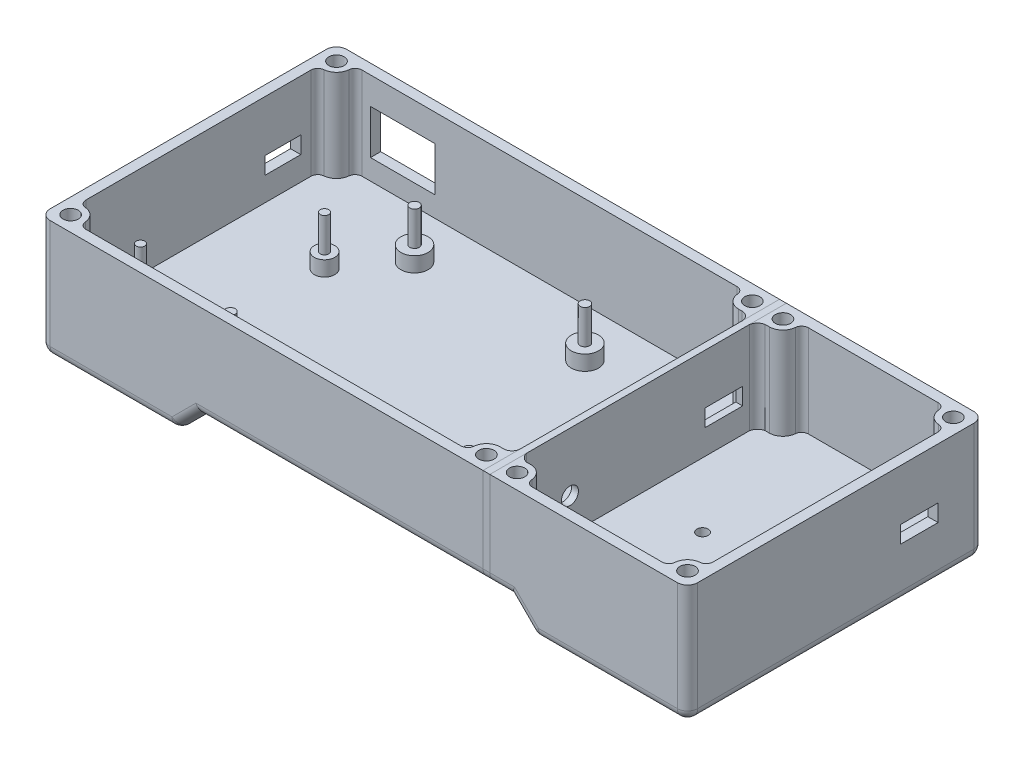
SolidWorks part; units mm, degrees
ref_plane "Front Plane" through (0, 0, 0) normal (0, 0, 1) x (1, 0, 0)
ref_plane "Top Plane" through (0, 0, 0) normal (0, 1, 0) x (1, 0, 0)
ref_plane "Right Plane" through (0, 0, 0) normal (1, 0, 0) x (0, 0, -1)
sketch "Sketch1" plane through (0, 0, 0) normal (0, 1, 0) x (1, 0, 0)
  line L0 (39, 43.5) -> (39, -43.5)
  line L1 (-89, -43.5) -> (89, -43.5)
  line L2 (-89, -43.5) -> (-89, 43.5)
  line L3 (-89, 43.5) -> (89, 43.5)
  line L4 (89, -43.5) -> (89, 43.5)
  line L5 (-89, -43.5) -> (89, 43.5) construction
  line L6 (-89, 43.5) -> (89, -43.5) construction
  line L7 (41, 43.5) -> (41, -43.5)
  point P0 (0, 0)
  dimension "D1" = 178
  dimension "D2" = 87
  dimension "D3" = 128
  dimension "D4" = 48
extrude "Boss-Extrude1" add sketch "Sketch1" along normal mid plane 35 contours L3 L2 L1 L0 region at (-25, 0, 0)
extrude "Boss-Extrude3" add sketch "Sketch1<4>" along normal mid plane 35 separate body contours L3 L7 L1 L4 region at (65, 0, 0)
sketch "Sketch1<4>" plane through (0, 0, 0) normal (0, 1, 0) x (1, 0, 0) same geometry as "Sketch1"
extrude "Boss-Extrude4" add sketch "Sketch1<5>" along normal mid plane 35 separate body contours L7 L3 L0 L1 region at (40, 0, 0)
sketch "Sketch1<5>" plane through (0, 0, 0) normal (0, 1, 0) x (1, 0, 0) same geometry as "Sketch1"
sketch "Sketch2" plane through (0, 17.5, 0) normal (0, 1, 0) x (1, 0, 0)
  line L0 (-89, -43.5) -> (-89, 43.5) construction
  line L1 (-89, 43.5) -> (39, 43.5) construction
  line L2 (-89, -43.5) -> (39, -43.5) construction
  line L3 (39, 43.5) -> (39, -43.5) construction
  point P0 (-84.5, 39)
  point P1 (35.5, -39)
  point P2 (-84.5, -39)
  point P3 (35.5, 39)
  dimension "D1" = 4.5
  dimension "D2" = 4.5
  dimension "D3" = 4.5
  dimension "D4" = 3.5
sketch "Sketch5" plane through (0, 17.5, 0) normal (0, 1, 0) x (1, 0, 0)
  line L0 (41, 43.5) -> (41, -43.5) construction
  line L1 (89, -43.5) -> (89, 43.5) construction
  line L2 (41, -43.5) -> (89, -43.5) construction
  line L3 (41, 43.5) -> (89, 43.5) construction
  point P0 (44.5, 39)
  point P1 (84.5, 39)
  point P2 (44.5, -39)
  point P3 (84.5, -39)
  dimension "D2" = 4.5
  dimension "D3" = 4.5
  dimension "D1" = 3.5
  dimension "D4" = 4.5
sketch "Sketch8" plane through (0, 17.5, 0) normal (0, 1, 0) x (1, 0, 0)
  line L0 (89, -43.5) -> (89, 43.5) construction
  line L1 (48.2081, -40.5) -> (80.7919, -40.5)
  line L2 (41, -32.6771) -> (41, 32.6771)
  line L3 (48.2081, 40.5) -> (80.7919, 40.5)
  line L4 (86, -35.2919) -> (86, 35.2919)
  line L5 (43.9355, -35.0001) -> (83.1881, 35.2213) construction
  line L6 (43.9355, 35.0001) -> (83.1881, -35.2213) construction
  line L7 (41, -43.5) -> (89, -43.5) construction
  line L8 (41, 43.5) -> (41, -43.5) construction
  line L10 (43.2532, 35.0001) -> (44.5308, 35.0001)
  line L11 (-93.9988, 0) -> (111.049, 0) construction
  line L12 (43.2532, -35.0001) -> (44.5308, -35.0001)
  arc A0 (80.7919, 40.5) -> (86, 35.2919) centre (84.5, 39) ccw
  arc A1 (48.2081, 40.5) -> (44.5308, 35.0001) centre (44.5, 39) cw
  arc A2 (43.2532, 35.0001) -> (41, 32.6771) centre (43.8563, 32.1609) ccw
  arc A3 (80.7919, -40.5) -> (86, -35.2919) centre (84.5, -39) cw
  arc A4 (43.2532, -35.0001) -> (41, -32.6771) centre (43.8563, -32.1609) cw
  arc A5 (48.2081, -40.5) -> (44.5308, -35.0001) centre (44.5, -39) ccw
  point P0 (63.5, 0)
  dimension "D7" = 4
  dimension "D2" = 3
  dimension "D3" = 3
  dimension "D4" = 0
extrude "Cut-Extrude1" cut sketch "Sketch8" against normal offset from surface (27 mm away) 8 up to face at (65, -17.5, 0)
fillet "Fillet1" radius 2 6 edges at (48.2081, 4, 40.5) (80.7919, 4, 40.5) (86, 4, 35.2919) (80.7919, 4, -40.5) (86, 4, -35.2919) (48.2081, 4, -40.5)
sketch "Sketch10" plane through (0, 17.5, 0) normal (0, 1, 0) x (1, 0, 0)
  line L0 (-89, 43.5) -> (39, 43.5) construction
  line L1 (-80.7919, -40.5) -> (31.7919, -40.5)
  line L2 (-86, -35.2919) -> (-86, 35.2919)
  line L3 (-80.7919, 40.5) -> (31.7919, 40.5)
  line L4 (39, -32.5) -> (39, 32.5)
  line L5 (-80.9229, -37.21) -> (32.5375, 36.3123) construction
  line L6 (-80.9229, 37.21) -> (32.5375, -36.3123) construction
  line L7 (-89, -43.5) -> (-89, 43.5) construction
  line L8 (39, 43.5) -> (39, -43.5) construction
  line L10 (35.5, 35) -> (36.5, 35)
  line L11 (-113.4699, 0) -> (103.1317, 0) construction
  line L12 (35.5, -35) -> (36.5, -35)
  arc A0 (-80.7919, 40.5) -> (-86, 35.2919) centre (-84.5, 39) cw
  arc A1 (31.7919, 40.5) -> (35.5, 35) centre (35.5, 39) ccw
  arc A2 (36.5, 35) -> (39, 32.5) centre (36.5, 32.5) cw
  arc A3 (31.7919, -40.5) -> (35.5, -35) centre (35.5, -39) cw
  arc A4 (36.5, -35) -> (39, -32.5) centre (36.5, -32.5) ccw
  arc A5 (-80.7919, -40.5) -> (-86, -35.2919) centre (-84.5, -39) ccw
  point P0 (-23.5, 0)
  dimension "D5" = 2.5
  dimension "D2" = 3
  dimension "D3" = 3
  dimension "D4" = 0
extrude "Cut-Extrude2" cut sketch "Sketch10" against normal offset from surface (27 mm away) 8 up to face at (-25, -17.5, 0)
fillet "Fillet2" radius 2 6 edges at (31.7919, 4, 40.5) (-80.7919, 4, 40.5) (-86, 4, 35.2919) (-80.7919, 4, -40.5) (-86, 4, -35.2919) (31.7919, 4, -40.5)
sketch "Sketch11" plane through (0, -9.5, 0) normal (0, 1, 0) x (1, 0, 0)
  line L0 (-78.5209, -40.5) -> (29.5209, -40.5) construction
  line L2 (-86, -33.0209) -> (-86, 33.0209) construction
  line L4 (-86, 33.0209) -> (-86, -33.0209) construction
  circle A0 centre (-51.05, 26.45) radius 4
  circle A1 centre (-1.05, 26.45) radius 4
  circle A2 centre (-51.05, -27.55) radius 4
  circle A3 centre (18.95, -27.55) radius 3.5
  circle A4 centre (-62.5, 11.5) radius 3
  circle A5 centre (-79.5, -23.5) radius 3
  point P22 (-79.5, -23.5)
  dimension "D3" = 8
  dimension "D4" = 7
  dimension "D8" = 8
  dimension "D9" = 8
  dimension "D14" = 6
  dimension "D2" = 54
  dimension "D10" = 6
  dimension "D6" = 35
  dimension "D1" = 12.95
  dimension "D5" = 34.95
  dimension "D7" = 17
  dimension "D12" = 6.5
  dimension "D13" = 17
  dimension "D15" = 70
  dimension "D16" = 50
extrude "Boss-Extrude5" add sketch "Sketch11" along normal blind 4.4
ref_plane "Plane1" through (0, -5.1, 0) normal (0, 1, 0) x (1, 0, 0)
sketch "Sketch12" plane through (0, -5.1, 0) normal (0, 1, 0) x (1, 0, 0)
  circle A0 centre (-51.05, 26.45) radius 1.4
  circle A1 centre (-51.05, 26.45) radius 4 construction
  circle A2 centre (-1.05, 26.45) radius 1.4
  circle A3 centre (18.95, -27.55) radius 1.4
  circle A4 centre (-51.05, -27.55) radius 1.4
  circle A5 centre (-62.5, 11.5) radius 1.25
  circle A7 centre (-1.05, 26.45) radius 4 construction
  circle A8 centre (18.95, -27.55) radius 3.5 construction
  circle A9 centre (-51.05, -27.55) radius 4 construction
  circle A10 centre (-62.5, 11.5) radius 3 construction
  circle A11 centre (-79.5, -23.5) radius 1.25
  dimension "D8" = 2.5
  dimension "D9" = 2.8
  dimension "D10" = 2.8
  dimension "D11" = 2.8
  dimension "D12" = 2.8
  dimension "D6" = 2.5
  dimension "D1" = 0
  dimension "D2" = 0
  dimension "D3" = 0
  dimension "D4" = 0
  dimension "D5" = 0
sketch "Sketch17" plane through (41, 0, 0) normal (1, 0, 0) x (0, 0, -1)
  line L0 (0, 23.5982) -> (0, -22.9808) construction
  line L1 (32.6771, -9.5) -> (32.6771, 17.5) construction
  line L2 (19.6771, -2.1913) -> (30.6771, -2.1913)
  line L3 (19.6771, -2.1913) -> (19.6771, 2.8087)
  line L4 (19.6771, 2.8087) -> (30.6771, 2.8087)
  line L5 (30.6771, -2.1913) -> (30.6771, 2.8087)
  line L6 (19.6771, -2.1913) -> (30.6771, 2.8087) construction
  line L7 (19.6771, 2.8087) -> (30.6771, -2.1913) construction
  circle A0 centre (-20, 0.3087) radius 2.5
  dimension "D1" = 5
  dimension "D3" = 20
  dimension "D2" = 2
  dimension "D4" = 11
  dimension "D5" = 5
extrude "Cut-Extrude4" cut sketch "Sketch17" against normal blind 10
sketch "Sketch21" plane through (-86, 0, 0) normal (1, 0, 0) x (0, 0, -1)
  line L2 (19.5209, -2.5) -> (30.0209, -2.5)
  line L3 (19.5209, -2.5) -> (19.5209, 2.5)
  line L4 (19.5209, 2.5) -> (30.0209, 2.5)
  line L5 (30.0209, -2.5) -> (30.0209, 2.5)
  line L6 (19.5209, -2.5) -> (30.0209, 2.5) construction
  line L7 (19.5209, 2.5) -> (30.0209, -2.5) construction
  dimension "D3" = 10.5
  dimension "D4" = 5
sketch "Sketch24" plane through (0, 0, -40.5) normal (0, 0, 1) x (1, 0, 0)
  line L0 (-78.5209, 17.5) -> (-78.5209, -9.5) construction
  line L1 (-78.0209, -3.5) -> (-59.0209, -3.5)
  line L2 (-78.0209, -3.5) -> (-78.0209, 9.5)
  line L3 (-78.0209, 9.5) -> (-59.0209, 9.5)
  line L4 (-59.0209, -3.5) -> (-59.0209, 9.5)
  line L5 (-78.0209, -3.5) -> (-59.0209, 9.5) construction
  line L6 (-78.0209, 9.5) -> (-59.0209, -3.5) construction
  line L7 (-78.5209, -9.5) -> (29.5209, -9.5) construction
  point P0 (-68.5209, 3)
  dimension "D1" = 13
  dimension "D2" = 19
  dimension "D3" = 0.5
  dimension "D4" = 6
sketch "Sketch25" plane through (0, 17.5, 0) normal (0, 1, 0) x (1, 0, 0)
  circle A0 centre (44.5, 39) radius 2.25
  circle A1 centre (84.5, 39) radius 2.25
  circle A2 centre (84.5, -39) radius 2.25
  circle A3 centre (44.5, -39) radius 2.25
  dimension "D1" = 4.5
  dimension "D2" = 4.5
  dimension "D3" = 4.5
  dimension "D4" = 4.5
extrude "Cut-Extrude8" cut sketch "Sketch25" against normal blind 12
sketch "Sketch26" plane through (0, 17.5, 0) normal (0, 1, 0) x (1, 0, 0)
  circle A0 centre (35.5, -39) radius 2.25
  circle A1 centre (-84.5, -39) radius 2.25
  circle A2 centre (-84.5, 39) radius 2.25
  circle A3 centre (35.5, 39) radius 2.25
  dimension "D1" = 4.5
  dimension "D2" = 4.5
  dimension "D3" = 4.5
  dimension "D4" = 4.5
extrude "Boss-Extrude6" add sketch "Sketch12" along normal blind 10
extrude "Cut-Extrude11" cut sketch "Sketch21" against normal through all
extrude "Cut-Extrude12" cut sketch "Sketch26" against normal blind 12
ref_plane "Plane3" through (-75, 0, 0) normal (-1, 0, 0) x (0, 0, 1)
split "Split2" trim tools "Plane3" bodies to split 130 resulting bodies 131 132
move or copy body "Body-Move/Copy3" bodies to move or copy 131 copy no translate (-2, 0, 0)
sketch "Sketch29" plane through (-77, 0, 0) normal (1, 0, 0) x (0, 0, -1)
  line L8 (43.5, -17.5) -> (43.5, 17.5)
  line L9 (43.5, 17.5) -> (40.5, 17.5)
  line L10 (40.5, 17.5) -> (40.5, -9.5)
  line L11 (40.5, -9.5) -> (-40.5, -9.5)
  line L12 (-40.5, -9.5) -> (-40.5, 17.5)
  line L13 (-40.5, 17.5) -> (-43.5, 17.5)
  line L14 (-43.5, 17.5) -> (-43.5, -17.5)
  line L15 (-43.5, -17.5) -> (43.5, -17.5)
  line L16 (43.5, -17.5) -> (43.5, 17.5)
  line L17 (43.5, 17.5) -> (40.5, 17.5)
  line L18 (40.5, 17.5) -> (40.5, -9.5)
  line L19 (40.5, -9.5) -> (-40.5, -9.5)
  line L20 (-40.5, -9.5) -> (-40.5, 17.5)
  line L21 (-40.5, 17.5) -> (-43.5, 17.5)
  line L22 (-43.5, 17.5) -> (-43.5, -17.5)
  line L23 (-43.5, -17.5) -> (43.5, -17.5)
  dimension "D1" = 0
extrude "Boss-Extrude8" add sketch "Sketch29" along normal blind 2
extrude "Cut-Extrude13" cut sketch "Sketch24" against normal through all
ref_plane "Plane4" through (65, 0, 0) normal (1, 0, 0) x (0, 0, -1)
split "Split3" trim tools "Plane4" bodies to split 118 resulting bodies 136 137
move or copy body "Body-Move/Copy5" bodies to move or copy 136 copy no translate (10, 0, 0)
sketch "Sketch31" plane through (65, 0, 0) normal (1, 0, 0) x (0, 0, -1)
  line L8 (43.5, 17.5) -> (40.5, 17.5)
  line L9 (40.5, 17.5) -> (40.5, -9.5)
  line L10 (40.5, -9.5) -> (-40.5, -9.5)
  line L11 (-40.5, -9.5) -> (-40.5, 17.5)
  line L12 (-40.5, 17.5) -> (-43.5, 17.5)
  line L13 (-43.5, 17.5) -> (-43.5, -17.5)
  line L14 (-43.5, -17.5) -> (43.5, -17.5)
  line L15 (43.5, -17.5) -> (43.5, 17.5)
  line L16 (43.5, 17.5) -> (40.5, 17.5)
  line L17 (40.5, 17.5) -> (40.5, -9.5)
  line L18 (40.5, -9.5) -> (-40.5, -9.5)
  line L19 (-40.5, -9.5) -> (-40.5, 17.5)
  line L20 (-40.5, 17.5) -> (-43.5, 17.5)
  line L21 (-43.5, 17.5) -> (-43.5, -17.5)
  line L22 (-43.5, -17.5) -> (43.5, -17.5)
  line L23 (43.5, -17.5) -> (43.5, 17.5)
  dimension "D1" = 0
extrude "Boss-Extrude9" add sketch "Sketch31" along normal blind 13
sketch "Sketch32" plane through (0, 0, -43.5) normal (0, 0, -1) x (-1, 0, 0)
  line L0 (0, 32.4254) -> (0, -34.019) construction
  line L1 (91, -17.5) -> (-39, -17.5) construction
  line L2 (-31, -10.5) -> (-12, -10.5)
  line L3 (-31, -10.5) -> (-31, -14.5)
  line L4 (-31, -14.5) -> (-12, -14.5)
  line L5 (-12, -10.5) -> (-12, -14.5)
  line L10 (-12, -14.5) -> (-8, -10.5)
  line L11 (-8, -10.5) -> (-12, -10.5)
  line L12 (-31, -14.5) -> (-35, -10.5)
  line L13 (-35, -10.5) -> (-31, -10.5)
  line L14 (35, -10.5) -> (31, -10.5)
  line L15 (31, -14.5) -> (35, -10.5)
  line L16 (31, -14.5) -> (12, -14.5)
  line L17 (12, -14.5) -> (8, -10.5)
  line L18 (8, -10.5) -> (12, -10.5)
  line L19 (31, -10.5) -> (12, -10.5)
  dimension "D1" = 19
  dimension "D2" = 4
  dimension "D3" = 3
  dimension "D4" = 12
  dimension "D5" = 45
extrude "Cut-Extrude17" cut sketch "Sketch32" against normal through all contours L13 L12 L3 | L5 L2 L3 L4 | L10 L11 L5 | L14 L19 L18 L17 L16 L15 region at (21.5, -12.5, -43.5) region at (32.3333, -11.8333, -43.5) region at (10.6667, -11.8333, -43.5)
sketch "Sketch36" plane through (0, 0, -43.5) normal (0, 0, -1) x (-1, 0, 0)
  line L0 (-5, -10.5) -> (5, -10.5)
  line L1 (-39, 17.5) -> (-39, -17.5) construction
  line L2 (-39, -10.5) -> (-39, -17.5)
  line L3 (-39, 17.5) -> (-39, -17.5) construction
  line L4 (-39, -17.5) -> (91, -17.5)
  line L5 (31, -17.5) -> (51, -17.5)
  line L7 (44, -10.5) -> (38, -10.5)
  line L8 (-39, -10.5) -> (-38, -10.5)
  line L9 (-31, -17.5) -> (-38, -10.5)
  line L10 (-31, -14.5) -> (-35, -10.5) construction
  line L11 (-12, -17.5) -> (-5, -10.5)
  line L12 (-12, -14.5) -> (-8, -10.5) construction
  line L13 (5, -10.5) -> (12, -17.5)
  line L14 (38, -10.5) -> (31, -17.5)
  line L15 (44, -10.5) -> (51, -17.5)
  line M13 (-39, -17.5) -> (91, -17.5)
  line M16 (-39, 17.5) -> (-39, -17.5)
  dimension "D1" = 3
  dimension "D2" = 3
  dimension "D3" = 3
  dimension "D4" = 3
  dimension "D5" = 40
  dimension "D6" = 45
extrude "Cut-Extrude18" cut sketch "Sketch36" against normal through all contours L13 L0 L11 M13 | L9 L8 M13 M16 | L15 L7 L14 L4 | L5 L15 L7 L14 region at (-41, -14.6282, -43.5) region at (36.2963, -14.9074, -43.5) region at (0, -14.4804, -43.5)
sketch "Sketch37" plane through (0, 0, -43.5) normal (0, 0, -1) x (-1, 0, 0)
  line L0 (-41, 17.5) -> (-41, -17.5) construction
  line L1 (-99, -17.5) -> (-41, -17.5)
  line L2 (-99, -17.5) -> (-99, -10.5)
  line L3 (-99, -10.5) -> (-41, -10.5)
  line L4 (-41, -17.5) -> (-41, -10.5)
  line L5 (-54, -17.5) -> (-47, -10.5)
  line M4 (-41, -17.5) -> (-41, 17.5)
  dimension "D1" = 7
  dimension "D2" = 45
  dimension "D3" = 45
extrude "Cut-Extrude19" cut sketch "Sketch37" against normal through all contours L5 L1 L3 M4 region at (45.9649, -14.4298, -43.5)
sketch "Sketch38" plane through (0, 0, -43.5) normal (0, 0, -1) x (-1, 0, 0)
  line L1 (-41, -17.5) -> (-39, -17.5)
  line L2 (-41, -17.5) -> (-41, -10.5)
  line L3 (-41, -10.5) -> (-39, -10.5)
  line L4 (-39, -17.5) -> (-39, -10.5)
extrude "Cut-Extrude20" cut sketch "Sketch38" against normal through all
sketch "Sketch39" plane through (0, -17.5, 0) normal (0, -1, 0) x (1, 0, 0)
  line L0 (38, 43.5) -> (38, -43.5) construction
  line L1 (5, 43.5) -> (38, 43.5)
  line L2 (5, 43.5) -> (5, 10)
  line L3 (5, 10) -> (38, 10)
  line L4 (38, 43.5) -> (38, 10)
  line L5 (0, 50.1636) -> (0, -55.4936) construction
  line L6 (-105.9786, 0) -> (119.626, 0) construction
  line L7 (5, -43.5) -> (38, -43.5)
  line L8 (38, -43.5) -> (38, -10)
  line L9 (5, -10) -> (38, -10)
  line L10 (5, -43.5) -> (5, -10)
  line L11 (-5, -43.5) -> (-5, -10)
  line L12 (-5, -10) -> (-38, -10)
  line L13 (-38, -43.5) -> (-38, -10)
  line L14 (-5, -43.5) -> (-38, -43.5)
  line L15 (-38, 43.5) -> (-38, 10)
  line L16 (-5, 10) -> (-38, 10)
  line L17 (-5, 43.5) -> (-5, 10)
  line L18 (-5, 43.5) -> (-38, 43.5)
  dimension "D1" = 33.5
extrude "Cut-Extrude21" cut sketch "Sketch39" against normal blind 7
sketch "Sketch40" plane through (0, -9.5, 0) normal (0, 1, 0) x (1, 0, 0)
  line L0 (69.5, 40.5) -> (69.5, -40.5) construction
  line L1 (50.4791, 40.5) -> (88.5209, 40.5) construction
  line L2 (88.5209, -40.5) -> (50.4791, -40.5) construction
  line L3 (41, 0) -> (96, 0) construction
  line L4 (41, 43.5) -> (41, -43.5) construction
  line L5 (96, 33.0209) -> (96, -33.0209) construction
  circle A0 centre (59.9, 0) radius 1.65
  circle A1 centre (79.1, 0) radius 1.65
  dimension "D1" = 3.3
  dimension "D2" = 9.6
extrude "Cut-Extrude22" cut sketch "Sketch40" against normal through all
sketch "Sketch41" plane through (0, -17.5, 0) normal (0, -1, 0) x (1, 0, 0)
  line L1 (59.9, 3.3198) -> (57.025, 1.6599)
  line L2 (57.025, 1.6599) -> (57.025, -1.6599)
  line L3 (57.025, -1.6599) -> (59.9, -3.3198)
  line L4 (59.9, -3.3198) -> (62.775, -1.6599)
  line L5 (62.775, -1.6599) -> (62.775, 1.6599)
  line L6 (62.775, 1.6599) -> (59.9, 3.3198)
  line L7 (79.1, 3.3198) -> (76.225, 1.6599)
  line L8 (76.225, 1.6599) -> (76.225, -1.6599)
  line L9 (76.225, -1.6599) -> (79.1, -3.3198)
  line L10 (79.1, -3.3198) -> (81.975, -1.6599)
  line L11 (81.975, -1.6599) -> (81.975, 1.6599)
  line L12 (81.975, 1.6599) -> (79.1, 3.3198)
  circle A0 centre (59.9, 0) radius 2.875 construction
  circle A1 centre (79.1, 0) radius 2.875 construction
  dimension "D1" = 5.75
  dimension "D2" = 5.75
extrude "Cut-Extrude23" cut sketch "Sketch41" against normal blind 3
sketch "Sketch42" plane through (96, 0, 0) normal (-1, 0, 0) x (0, 0, 1)
  line L0 (-33.0209, 17.5) -> (-33.0209, -9.5) construction
  line L1 (-30.0209, -2.5) -> (-19.0209, -2.5)
  line L2 (-30.0209, -2.5) -> (-30.0209, 2.5)
  line L3 (-30.0209, 2.5) -> (-19.0209, 2.5)
  line L4 (-19.0209, -2.5) -> (-19.0209, 2.5)
  line L5 (-30.0209, -2.5) -> (-19.0209, 2.5) construction
  line L6 (-30.0209, 2.5) -> (-19.0209, -2.5) construction
  point P0 (-24.5209, 0)
  dimension "D1" = 11
  dimension "D2" = 5
  dimension "D3" = 3
extrude "Cut-Extrude24" cut sketch "Sketch42" against normal through all
fillet "Fillet3" radius 3 10 edges at (-51, -17.5, 0) (-47.5, -14, -43.5) (-2.5, -10.5, -43.5) (-47.5, -14, 43.5) (-2.5, -10.5, 43.5) (-71, -17.5, 43.5) (-71, -17.5, -43.5) (-91, -17.5, 0) (-91, 0, 43.5) (-91, 0, -43.5)
fillet "Fillet4" radius 3 2 edges at (40, -10.5, 43.5) (40, -10.5, -43.5)
fillet "Fillet5" radius 3 8 edges at (44, -10.5, 43.5) (50.5, -14, 43.5) (76.5, -17.5, 43.5) (99, -17.5, 0) (76.5, -17.5, -43.5) (50.5, -14, -43.5) (44, -10.5, -43.5) (54, -17.5, 0)
fillet "Fillet6" radius 3 4 edges at (98.1213, -16.6213, 42.6213) (98.1213, -16.6213, -42.6213) (99, 1.5, 43.5) (99, 1.5, -43.5)
equation "\"D2@Sketch2\"=\"D1@Sketch2\""
equation "\"D3@Sketch2\"=\"D1@Sketch2\""
equation "\"D3@Sketch5\"=\"D2@Sketch5\""
equation "\"D4@Sketch5\"=\"D2@Sketch5\""
